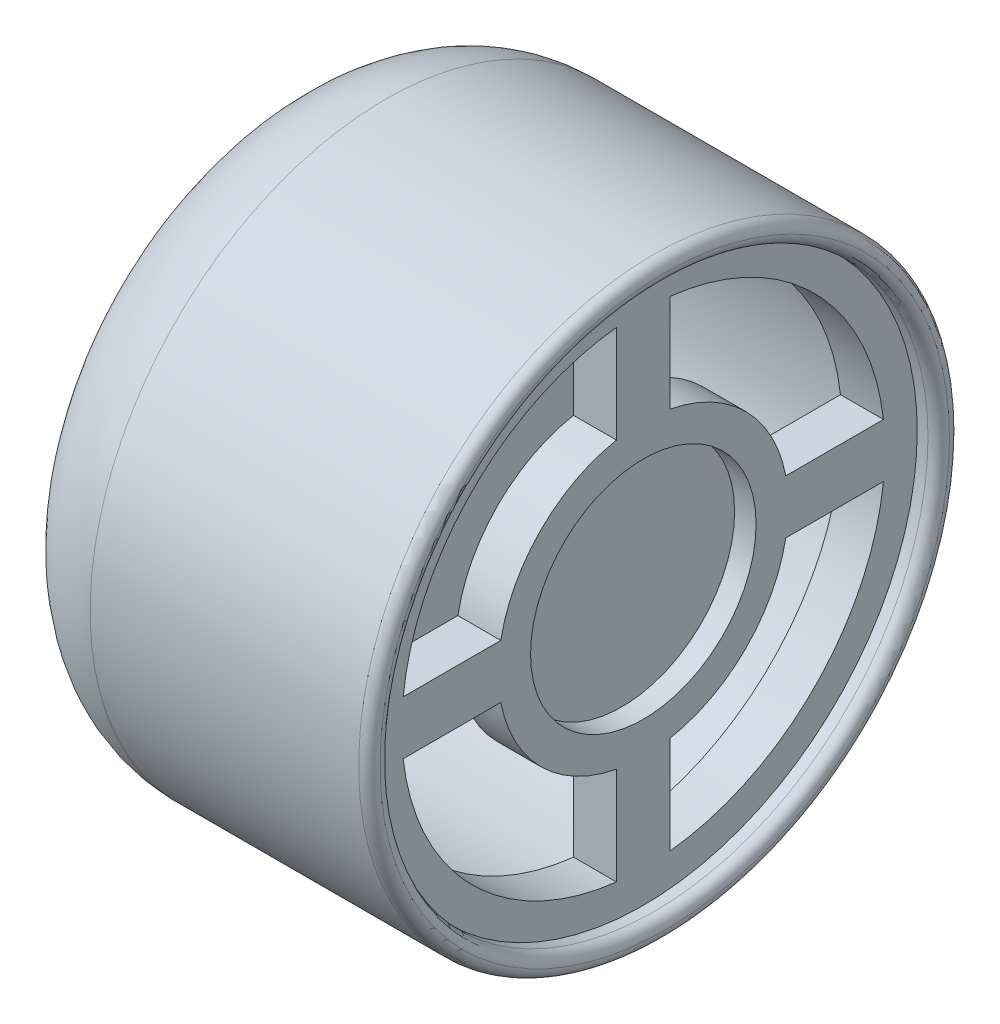
SolidWorks part; units mm, degrees
material "PLA"
ref_plane "Front Plane" through (0, 0, 0) normal (1, 0, 0) x (0, 1, 0)
ref_plane "Top Plane" through (0, 0, 0) normal (0, 0, 1) x (0, 1, 0)
ref_plane "Right Plane" through (0, 0, 0) normal (0, 1, 0) x (-1, 0, 0)
sketch "Sketch1" plane through (0, 0, 0) normal (1, 0, 0) x (0, 1, 0)
  line L0 (0, 6.5) -> (-20.5, 6.5)
  line L1 (0, 6.5) -> (0, -6.5)
  line L2 (0, -6.5) -> (-20.5, -6.5)
  line L3 (-20.5, 6.5) -> (-20.5, -6.5)
  line L4 (0, 0) -> (-24.2656, 0) construction
  line L5 (0, 6.5) -> (0, -6.5)
  line L6 (0, 19.7112) -> (0, -27.6906) construction
  line L7 (-16.5, 6.5) -> (7.5, 6.5)
  line L8 (-16.5, 6.5) -> (-16.5, -6.5)
  line L9 (-16.5, -6.5) -> (7.5, -6.5)
  line L10 (7.5, 6.5) -> (7.5, -6.5)
  circle A0 centre (0, 0) radius 10.25
  circle A1 centre (0, 0) radius 21.5058
  circle A3 centre (0, 0) radius 25.5058
  circle A4 centre (0, 0) radius 27.5058
  dimension "D1" = 20.5
  dimension "D2" = 20.5
  dimension "D3" = 13
  dimension "D4" = 24
  dimension "D5" = 7.5
  dimension "D6" = 4
  dimension "D7" = 2
extrude "Boss-Extrude1" add sketch "Sketch1" along normal blind 30 contours A4 A3 region at (0, -26.7278, 0)
sketch "Sketch2" plane through (30, 0, 0) normal (1, 0, 0) x (0, 1, 0)
  circle A0 centre (0, 0) radius 10.5
  circle A1 centre (0, 0) radius 27.5058
  circle A2 centre (0, 0) radius 27.5058
  circle M3 centre (0, 0) radius 25.5058
  circle M4 centre (0, 0) radius 27.5058
  dimension "D2" = 21
  dimension "D1" = 0
extrude "Boss-Extrude4" add sketch "Sketch2" along normal blind 6 contours M4 M3 region at (30, -26.7278, 0)
extrude "Boss-Extrude5" add sketch "Sketch2<4>" along normal blind 4 contours A0 M3 region at (30, -24.7844, 0)
sketch "Sketch2<4>" plane through (30, 0, 0) normal (1, 0, 0) x (0, 1, 0) same geometry as "Sketch2"
extrude "Boss-Extrude6" add sketch "Sketch2<5>" along normal blind 2 contours A0 region at (30, 0, 0)
sketch "Sketch2<5>" plane through (30, 0, 0) normal (1, 0, 0) x (0, 1, 0) same geometry as "Sketch2"
sketch "Sketch3" plane through (0, 0, 0) normal (-1, 0, 0) x (0, -1, 0)
  line L0 (0, 6.5) -> (-20.5, 6.5)
  line L1 (0, 6.5) -> (0, -6.5)
  line L2 (0, -6.5) -> (-20.5, -6.5)
  line L3 (-20.5, 6.5) -> (-20.5, -6.5)
  line L4 (0, 0) -> (27.3238, 0) construction
  line L5 (0, 6.5) -> (0, -6.5)
  line L6 (0, 25.2285) -> (0, -22.1733) construction
  line L7 (-16.5, 6.5) -> (7.5, 6.5)
  line L8 (-16.5, 6.5) -> (-16.5, -6.5)
  line L9 (-16.5, -6.5) -> (7.5, -6.5)
  line L10 (7.5, 6.5) -> (7.5, -6.5)
  circle A0 centre (0, 0) radius 12.5
  circle A1 centre (0, 0) radius 25.5058 construction
  circle A2 centre (0, 0) radius 27.5058 construction
  circle A3 centre (0, 0) radius 25.5058
  circle A4 centre (0, 0) radius 27.5058
  circle A5 centre (0, 0) radius 4
  circle A6 centre (0, 0) radius 21.5058
  circle A7 centre (51.6169, 6.4587) radius 23.5058
  circle M1 centre (0, 0) radius 25.5058
  circle M2 centre (0, 0) radius 27.5058
  dimension "D1" = 25
  dimension "D2" = 8
  dimension "D3" = 20.5
  dimension "D4" = 13
  dimension "D5" = 24
  dimension "D6" = 7.5
extrude "Boss-Extrude8" add sketch "Sketch3" against normal blind 6 contours L2 A6 L0 L7 A0 L9 | L3 A6 | A6 M1 | L2 A0 L0 L7 L10 L9 | M2 M1 | L8 L0 L3 L2 region at (0, 18.5, 0) region at (0, 18.5, 7.1012) region at (0, 20.9031, 0) region at (0, -3.2833, 11.7074) region at (0, 24.7844, 0) region at (0, 26.7278, 0)
sketch "Sketch8" plane through (34, 0, 0) normal (1, 0, 0) x (0, 1, 0)
  line L0 (-2.5, 22.3607) -> (-2.5, -22.3607)
  line L1 (2.5, 22.3607) -> (2.5, -22.3607)
  line L2 (-22.3607, 2.5) -> (22.3607, 2.5)
  line L3 (-22.3607, -2.5) -> (22.3607, -2.5)
  circle A0 centre (0, 0) radius 13.5
  circle A1 centre (0, 0) radius 22.5
  circle A2 centre (0, 0) radius 10.5 construction
  dimension "D1" = 3
  dimension "D2" = 9
  dimension "D3" = 5
extrude "Cut-Extrude3" cut sketch "Sketch8" against normal up to next contours L3 A1 L0 A0 | L0 A1 L2 A0 | L2 A1 L1 A0 | L1 A1 L3 A0 region at (34, -12.1516, 12.1516) region at (34, 12.1516, 12.1516) region at (34, -12.1516, -12.1516) region at (34, 12.1516, -12.1516)
sketch "Sketch9" plane through (0, 0, 0) normal (-1, 0, 0) x (0, -1, 0)
  line L5 (-8.5, -8.5) -> (8.5, -8.5)
  line L6 (-8.5, -8.5) -> (-8.5, 8.5)
  line L7 (-8.5, 8.5) -> (8.5, 8.5)
  line L8 (8.5, -8.5) -> (8.5, 8.5)
  line L9 (0, 8.5) -> (0, -8.5) construction
  line L10 (-8.5, 0) -> (8.5, 0) construction
  circle A4 centre (-8.5, 8.5) radius 1
  circle A5 centre (8.5, 8.5) radius 1
  circle A6 centre (8.5, -8.5) radius 1
  circle A7 centre (-8.5, -8.5) radius 1
  point P0 (0, 0)
  dimension "D2" = 2
  dimension "D1" = 17
extrude "Cut-Extrude4" cut sketch "Sketch9" against normal up to next and the other way through all contours L7 A4 L6 | L6 A4 L7 | L6 A7 L5 | L5 A7 L6 | L5 A6 L8 | L8 A6 L5 | L8 A5 L7 | L7 A5 L8
fillet "Fillet9" radius 10 1 edges at (0, 0, -27.5058)
fillet "Fillet10" radius 1 2 edges at (36, 0, -25.5058) (36, 0, -27.5058)
